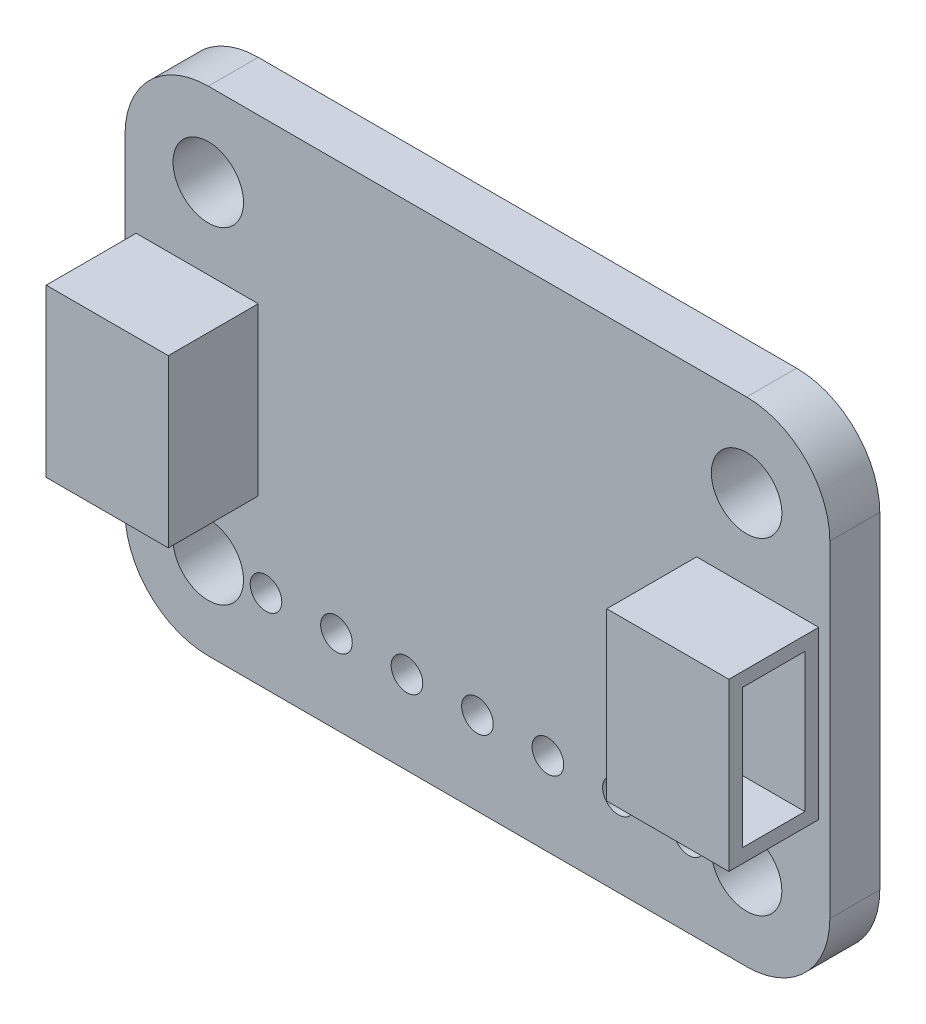
SolidWorks part; units mm, degrees
ref_plane "Alzado" through (0, 0, 0) normal (0, 0, 1) x (1, 0, 0)
ref_plane "Planta" through (0, 0, 0) normal (0, 1, 0) x (1, 0, 0)
ref_plane "Vista lateral" through (0, 0, 0) normal (1, 0, 0) x (0, 0, -1)
sketch "Croquis1" plane through (0, 0, 0) normal (0, 0, 1) x (1, 0, 0)
  line L0 (0, 8.89) -> (0, -8.89) construction
  line L1 (9.7, -8.89) -> (-9.7, -8.89)
  line L2 (12.7, -5.89) -> (12.7, 5.89)
  line L3 (9.7, 8.89) -> (-9.7, 8.89)
  line L4 (-12.7, -5.89) -> (-12.7, 5.89)
  line L5 (12.7, -8.89) -> (-12.7, 8.89) construction
  line L6 (12.7, 8.89) -> (-12.7, -8.89) construction
  line L7 (-12.7, 0) -> (12.7, 0) construction
  line L8 (7.62, -5.89) -> (-7.62, -5.89) construction
  line L9 (-7.62, -5.89) -> (-5.08, -5.89) construction
  arc A0 (9.7, -8.89) -> (12.7, -5.89) centre (9.7, -5.89) ccw
  arc A1 (-9.7, -8.89) -> (-12.7, -5.89) centre (-9.7, -5.89) cw
  arc A2 (12.7, 5.89) -> (9.7, 8.89) centre (9.7, 5.89) ccw
  arc A3 (-9.7, 8.89) -> (-12.7, 5.89) centre (-9.7, 5.89) ccw
  circle A4 centre (-9.7, 5.89) radius 1.27
  circle A5 centre (9.7, 5.89) radius 1.27
  circle A6 centre (9.7, -5.89) radius 1.27
  circle A7 centre (-9.7, -5.89) radius 1.27
  circle A13 centre (-7.62, -5.89) radius 0.57
  circle A14 centre (-5.08, -5.89) radius 0.57
  circle A15 centre (-2.54, -5.89) radius 0.57
  circle A16 centre (0, -5.89) radius 0.57
  circle A17 centre (2.54, -5.89) radius 0.57
  circle A18 centre (5.08, -5.89) radius 0.57
  circle A19 centre (7.62, -5.89) radius 0.57
  point P0 (0, 0)
  point P27 (0, 0)
  point P28 (-2.6066, -5.8252)
  point P29 (0, -4.8387)
  point P31 (0, -4.8387)
  dimension "D3" = 3
  dimension "D4" = 2.54
  dimension "D5" = 1.14
  dimension "D1" = 25.4
  dimension "D2" = 17.78
  dimension "D6" = 7
  dimension "D7" = 2.54
other "Alinear grupo1"
extrude "Saliente-Extruir1" add sketch "Croquis1" along normal blind 1.8
sketch "Croquis2" plane through (0, 0, 1.8) normal (0, 0, 1) x (1, 0, 0)
  line L1 (-7.9, -3) -> (-12.3, -3)
  line L2 (-7.9, -3) -> (-7.9, 3)
  line L3 (-7.9, 3) -> (-12.3, 3)
  line L4 (-12.3, -3) -> (-12.3, 3)
  line L5 (-7.9, -3) -> (-12.3, 3) construction
  line L6 (-7.9, 3) -> (-12.3, -3) construction
  line L7 (0, 8.89) -> (0, -8.89) construction
  line L8 (9.7, 8.89) -> (-9.7, 8.89) construction
  line L9 (-9.7, -8.89) -> (9.7, -8.89) construction
  line L10 (7.9, 3) -> (12.3, -3) construction
  line L11 (7.9, -3) -> (12.3, 3) construction
  line L12 (12.3, -3) -> (12.3, 3)
  line L13 (7.9, 3) -> (12.3, 3)
  line L14 (7.9, -3) -> (7.9, 3)
  line L15 (7.9, -3) -> (12.3, -3)
  line L16 (-12.7, 5.89) -> (-12.7, -5.89) construction
  point P0 (-10.1, 0)
  point P18 (-10.5, 0)
  dimension "D1" = 6
  dimension "D2" = 4.4
  dimension "D3" = 0.4
extrude "Saliente-Extruir2" add sketch "Croquis2" along normal blind 3.24
sketch "Croquis3" plane through (12.3, 0, 0) normal (1, 0, 0) x (0, 0, -1)
  line L0 (-2.3, -2.5) -> (-2.3, 2.5)
  line L1 (-2.3, 2.5) -> (-4.54, 2.5)
  line L2 (-4.54, 2.5) -> (-4.54, -2.5)
  line L3 (-4.54, -2.5) -> (-2.3, -2.5)
  line L4 (-1.8, -3) -> (-1.8, 3)
  line L5 (-1.8, 3) -> (-5.04, 3)
  line L6 (-5.04, 3) -> (-5.04, -3)
  line L7 (-5.04, -3) -> (-1.8, -3)
  line L8 (-1.8, -3) -> (-1.8, 3)
  line L9 (-1.8, 3) -> (-5.04, 3)
  line L10 (-5.04, 3) -> (-5.04, -3)
  line L11 (-5.04, -3) -> (-1.8, -3)
  dimension "D1" = 0
  dimension "D2" = 0.5
extrude "Cortar-Extruir2" cut sketch "Croquis3" against normal blind 3.9 contours L2 L3 L0 L1 region at (12.3, 0, 3.42)
extrude "Cortar-Extruir3" cut sketch "Croquis3<3>" along normal blind 3.9 from surface contours L2 L3 L0 L1 region at (12.3, 0, 3.42) starting at face at (-12.3, 0, 3.42)
sketch "Croquis3<3>" plane through (12.3, 0, 0) normal (1, 0, 0) x (0, 0, -1) same geometry as "Croquis3"
